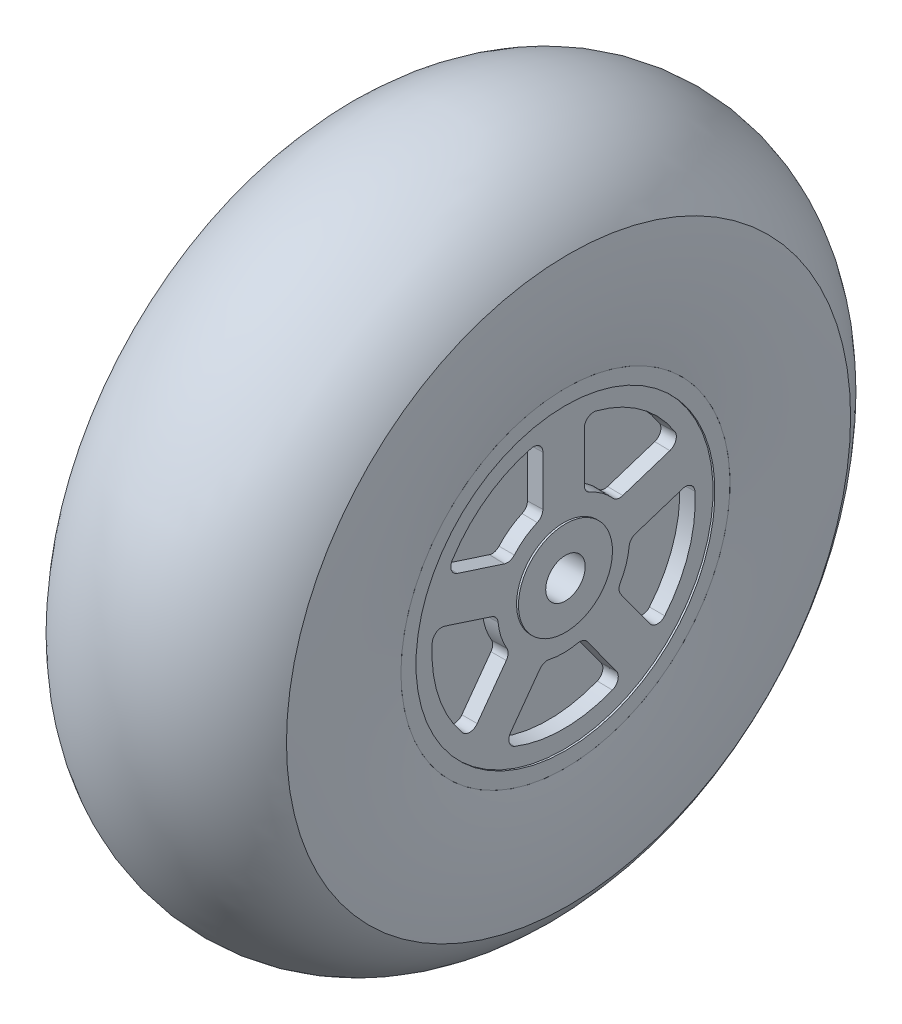
SolidWorks part; units mm, degrees
ref_plane "Front Plane" through (0, 0, 0) normal (0, 0, 1) x (1, 0, 0)
ref_plane "Top Plane" through (0, 0, 0) normal (0, 1, 0) x (1, 0, 0)
ref_plane "Right Plane" through (0, 0, 0) normal (1, 0, 0) x (0, 0, -1)
sketch "Sketch1" plane through (0, 0, 0) normal (0, 0, 1) x (1, 0, 0)
  line L0 (0, 0) -> (18.0131, 0) construction
  line L1 (12.1727, 17.5) -> (9, 14.4892)
  line L2 (9, 14.4892) -> (9, 7)
  line L3 (9, 7) -> (-9, 7)
  line L4 (12.1727, 17.5) -> (12.5, 30) construction
  line L5 (-9, 14.4892) -> (-9, 7)
  line L6 (-12.1727, 17.5) -> (-9, 14.4892)
  line L8 (0, 0) -> (0, 40.1179) construction
  arc A0 (-12.5, 30) -> (12.5, 30) centre (0, 22.3393) cw
  arc A1 (12.5, 30) -> (12.1727, 17.5) centre (-52.6402, 25.4515) cw
  arc A2 (-12.5, 30) -> (-12.1727, 17.5) centre (52.6402, 25.4515) ccw
  dimension "D1" = 1.5
  dimension "D2" = 74
  dimension "D3" = 45
  dimension "D4" = 0.3
  dimension "D5" = 35
  dimension "D6" = 25
  dimension "D7" = 14
  dimension "D8" = 30
  dimension "D9" = 18
revolve "Revolve1" add sketch "Sketch1" angle 360 about L0
sketch "Sketch3" plane through (0, 0, 0) normal (0, 0, 1) x (1, 0, 0)
  line L0 (-9, 14.4892) -> (-12.1727, 17.5) construction
  line L1 (-9, 14.4892) -> (-9, -14.4892) construction
  line L2 (-12.1727, 17.5) -> (-12.1727, -17.5) construction
  line L3 (-9, 14.4892) -> (-12.1727, 17.5)
  line L4 (-9, 14.4892) -> (-9, 7)
  line L5 (-12.1727, 17.5) -> (-12.1727, 15.9)
  line L7 (-9, 7) -> (9, 7)
  line L8 (0, 0) -> (0, 27.2869) construction
  line L9 (0, 0) -> (-18.7858, 0) construction
  line L10 (-12.1727, 15.9) -> (-11.9727, 15.9)
  line L11 (-11.9727, 15.9) -> (-11.9727, 5)
  line L12 (9, 7) -> (-9, 7) construction
  line L13 (-12.1727, 2.1) -> (12.1727, 2.1)
  line L14 (-11.9727, 5) -> (-12.1727, 5)
  line L15 (-12.1727, 5) -> (-12.1727, 2.1)
  line L16 (12.1727, 5) -> (12.1727, 2.1)
  line L17 (11.9727, 5) -> (12.1727, 5)
  line L18 (11.9727, 15.9) -> (11.9727, 5)
  line L19 (12.1727, 15.9) -> (11.9727, 15.9)
  line L20 (12.1727, 17.5) -> (12.1727, 15.9)
  line L21 (9, 14.4892) -> (9, 7)
  line L22 (9, 14.4892) -> (12.1727, 17.5)
  dimension "D1" = 4.2
  dimension "D2" = 1.6
  dimension "D3" = 0.2
  dimension "D4" = 10
revolve "Revolve2" add sketch "Sketch3" angle 360 about L9
sketch "Sketch2" plane through (-11.9727, 0, 0) normal (1, 0, 0) x (0, 0, -1)
  line L0 (2.2, 12.6) -> (2.2, 7.3321)
  line L1 (6.2934, 4.3581) -> (11.3035, 5.9859)
  line L2 (0, 0) -> (0, 9.1031) construction
  line L3 (0, 0) -> (8.4766, 2.7542) construction
  arc A0 (11.8402, 7.4706) -> (3.4462, 13.5692) centre (0, 0) ccw
  arc A1 (11.3035, 5.9859) -> (11.8402, 7.4706) centre (10.9945, 6.937) ccw
  arc A2 (5.2364, 4.6455) -> (2.8, 6.4156) centre (0, 0) ccw
  circle A3 centre (0, 0) radius 5 construction
  arc A4 (6.2934, 4.3581) -> (5.2364, 4.6455) centre (5.9844, 5.3091) cw
  arc A5 (2.2, 7.3321) -> (2.8, 6.4156) centre (3.2, 7.3321) ccw
  arc A6 (2.2, 12.6) -> (3.4462, 13.5692) centre (3.2, 12.6) cw
  dimension "D1" = 7
  dimension "D5" = 7
  dimension "D6" = 1
  dimension "D2" = 72
  dimension "D3" = 4.4
  dimension "D4" = 4.4
extrude "Extrude1" cut sketch "Sketch2" along normal blind 1.6 draft 1.5
pattern_circular "CirPattern1" count 5 over 360 of "Extrude1"
mirror "Mirror1" about plane through (0, 0, 0) normal (1, 0, 0) of "CirPattern1"
